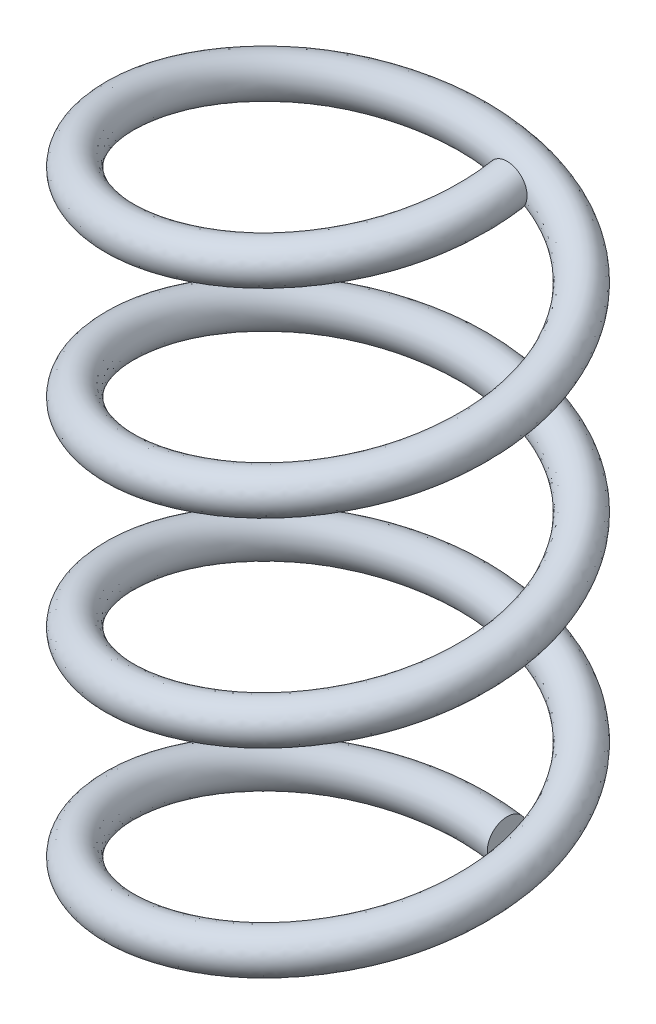
SolidWorks part; units mm, degrees
note: '?' marks a value the reader was unsure of.
material "AISI 304"
ref_plane "Front Plane" through (0, 0, 0) normal (0, 0, 1) x (1, 0, 0)
ref_plane "Top Plane" through (0, 0, 0) normal (0, 1, 0) x (1, 0, 0)
ref_plane "Right Plane" through (0, 0, 0) normal (1, 0, 0) x (0, 0, -1)
ref_axis "SpringAxis" through (0, 1.15, 0) along (0, -1, 0)?
sketch "SpringBodyDiameterS" plane through (0, 0, 0) normal (0, 0, 1) x (1, 0, 0)
  line L0 (0, 0) -> (1.6, 0) construction
  line L1 (0, 0) -> (0, 1) construction
  line L2 (1.8, 0) -> (2, 0) construction
  circle A0 centre (1.8, 0) radius 0.2
  dimension "WireDia" = 0.4
  dimension "RefRevolve" = 1
  dimension "RevolveDia" = 3.6
  dimension "RefID" = 3.2
  dimension "RefOD" = 4
sketch "SpringHelixS" plane through (0, 0, 0) normal (0, 1, 0) x (1, 0, 0)
  circle A0 centre (0, 0) radius 1.8
  dimension "RefDia" = 3.6
curve "SPRING HELIX" pitch 2 height 7.5 turns 3.75 parameters "Height"=7.5, "Pitch"=2
sweep "SPRING" add profiles "SpringBodyDiameterS" path "SPRING HELIX"
